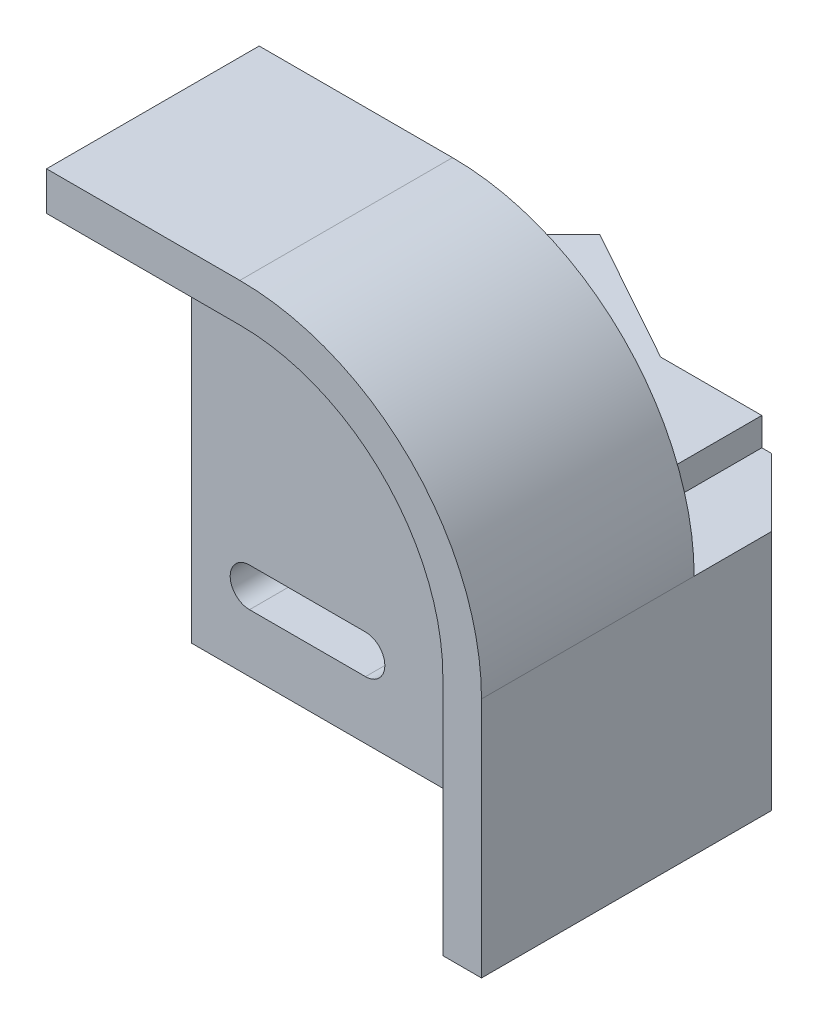
SolidWorks part; units mm, degrees
ref_plane "Front Plane" through (0, 0, 0) normal (0, 0, 1) x (1, 0, 0)
ref_plane "Top Plane" through (0, 0, 0) normal (0, 1, 0) x (1, 0, 0)
ref_plane "Right Plane" through (0, 0, 0) normal (1, 0, 0) x (0, 0, -1)
sketch "Sketch1" plane through (0, 0, 0) normal (0, 0, 1) x (1, 0, 0)
  line L0 (0, 25) -> (-20, 25)
  line L1 (-20, 25) -> (-20, -25)
  line L6 (-20, -25) -> (25, -25)
  line L7 (25, -25) -> (25, 0)
  arc A1 (25, 0) -> (0, 25) centre (0, 0) ccw
  dimension "D1" = 25
  dimension "D2" = 45
  dimension "D3" = 50
extrude "Boss-Extrude1" add sketch "Sketch1" along normal blind 7
sketch "Sketch3" plane through (0, 0, 7) normal (0, 0, 1) x (1, 0, 0)
  line L0 (25, -25) -> (25, 0) construction
  line L1 (0, 25) -> (-20, 25) construction
  line L2 (25, -25) -> (25, 0)
  line L3 (0, 25) -> (-20, 25)
  arc A0 (25, 0) -> (0, 25) centre (0, 0) ccw construction
  arc A1 (25, 0) -> (0, 25) centre (0, 0) ccw
extrude "Extrude-Thin2" add sketch "Sketch3" along normal blind 15 thin thin type one direction reverse wall 4
fillet "Fillet1" radius 7 3 edges at (-10, 21, 7) (14.8492, 14.8492, 7) (21, -12.5, 7)
sketch "Sketch5" plane through (25, 0, 0) normal (1, 0, 0) x (0, 0, -1)
  line L1 (0, -25) -> (15, -25)
  line L2 (0, -25) -> (0, 0)
  line L3 (0, 0) -> (15, 0)
  line L4 (15, -25) -> (15, 0)
  dimension "D1" = 15
extrude "Boss-Extrude2" add sketch "Sketch5" against normal blind 8
sketch "Sketch8" plane through (0, 0, 7) normal (0, 0, 1) x (1, 0, 0)
  line L0 (-20, -17) -> (-2, -17) construction
  line L1 (-20, 14) -> (-20, -25) construction
  line L2 (-20, -25) -> (14, -25) construction
  line L3 (-14, -15) -> (-2, -15)
  line L5 (-14, -19) -> (-2, -19)
  arc A0 (-2, -19) -> (-2, -15) centre (-2, -17) ccw
  arc A1 (-14, -15) -> (-14, -19) centre (-14, -17) ccw
  arc A2 (-2, -15) -> (-4, -17) centre (-2, -17) ccw construction
  arc A3 (-4, -17) -> (-2, -19) centre (-2, -17) ccw construction
  arc A4 (-12, -17) -> (-14, -15) centre (-14, -17) ccw construction
  arc A5 (-14, -19) -> (-12, -17) centre (-14, -17) ccw construction
  dimension "D1" = 4
  dimension "D2" = 12
  dimension "D3" = 6
  dimension "D4" = 8
extrude "Cut-Extrude2" cut sketch "Sketch8" against normal through all
pattern_linear "LPattern1" count 2 spacing 26 along (0, 1, 0) of "Cut-Extrude2"
chamfer "Chamfer3" distance 7 angle 45 1 edges at (25, -12.5, -15)
sketch "Sketch9" plane through (17, 0, 0) normal (-1, 0, 0) x (0, 0, 1)
  line L0 (0, 0) -> (0, -25) construction
  line L1 (-15, 0) -> (0, 0)
  line L2 (-15, 0) -> (-15, -7)
  line L3 (-15, -7) -> (0, -7)
  line L4 (0, 0) -> (0, -7)
  dimension "D1" = 7
extrude "Boss-Extrude3" add sketch "Sketch9" along normal blind 15
sketch "Sketch10" plane through (0, -7, 0) normal (0, -1, 0) x (1, 0, 0)
  line L0 (2, -15) -> (-6.9706, -15)
  line L1 (-6.9706, -15) -> (-12.6274, -9.3431)
  line L2 (-12.6274, -9.3431) -> (-16.8701, -13.5858)
  line L3 (-16.8701, -13.5858) -> (-20, -10.4558)
  line L4 (-6.9706, -7.9289) -> (-10.5061, -11.4645) construction
  line L5 (-20, -10.4558) -> (-20, 0)
  line L6 (-20, 0) -> (17, 0)
  line L7 (17, 0) -> (17, -15)
  line L8 (17, -15) -> (2, -15)
  line L9 (-4.8492, -10.0503) -> (-9.0919, -5.8076)
  line L10 (-9.0919, -5.8076) -> (-6.9706, -3.6863)
  line L11 (-6.9706, -3.6863) -> (-2.7279, -7.9289)
  line L12 (-2.7279, -7.9289) -> (-4.8492, -10.0503)
  line L14 (4.3431, -34.799) -> (-16.8701, -13.5858) construction
  dimension "D1" = 3
  dimension "D2" = 5
  dimension "D3" = 6
extrude "Boss-Extrude4" add sketch "Sketch10" against normal offset from surface 2 and the other way blind 2
sketch "Sketch13" plane through (-10.9853, 0, -10.9853) normal (-0.7071, 0, -0.7071) x (-0.7071, 0, 0.7071)
  line L0 (2.3223, -9) -> (2.3223, 2.9) construction
  line L1 (-5.6777, 2.9) -> (2.3223, 2.9)
  line L2 (-5.6777, 2.9) -> (-5.6777, 0.9)
  line L3 (-5.6777, 0.9) -> (2.3223, 0.9)
  line L4 (2.3223, 2.9) -> (2.3223, 0.9)
  line L5 (2.3223, 0.9) -> (-27.6777, 0.9) construction
  line L6 (2.3223, -9) -> (-5.6777, -9) construction
  line L7 (2.3223, -9) -> (-5.6777, -9)
  line L8 (2.3223, -9) -> (2.3223, -7)
  line L9 (2.3223, -7) -> (-5.6777, -7)
  line L10 (-5.6777, -9) -> (-5.6777, -7)
  line L11 (-5.6777, -9) -> (-5.6777, 2.9) construction
  line L12 (2.3223, -7) -> (-27.6777, -7) construction
extrude "Boss-Extrude6" add sketch "Sketch13" along normal up to surface (6 mm away) up to face at (-18.435, -3.05, -12.0208)
chamfer "Chamfer6" distance 13.5 angle 29 2 edges at (-6.9706, -8, -15) (-6.9706, 1.9, -15)
chamfer "Chamfer7" distance 3 angle 45 4 edges at (-1.5, 2.9, 0) (17, -9, -7.5) (17, -17, 0) (-1.5, -9, 0)
sketch "Sketch14" plane through (-10.9853, 0, -10.9853) normal (-0.7071, 0, -0.7071) x (-0.7071, 0, 0.7071)
  circle A0 centre (-0.6777, -3.05) radius 1.5
  dimension "D1" = 3
extrude "Cut-Extrude3" cut sketch "Sketch14" against normal blind 15
sketch "Sketch15" plane through (-15.2279, 0, -15.2279) normal (-0.7071, 0, -0.7071) x (-0.7071, 0, 0.7071)
  line L0 (2.3223, -7) -> (2.3223, 0.9) construction
  line L1 (2.6223, 1.2) -> (-12.3777, 1.2)
  line L2 (2.6223, 1.2) -> (2.6223, -7.3)
  line L3 (2.6223, -7.3) -> (-12.3777, -7.3)
  line L4 (-12.3777, 1.2) -> (-12.3777, -7.3)
  line L5 (-10.7659, -7) -> (2.3223, -7) construction
  line L6 (2.3223, 0.9) -> (-10.7659, 0.9) construction
  dimension "D1" = 0.3
  dimension "D2" = 15
  dimension "D3" = 0.3
  dimension "D4" = 0.3
extrude "Cut-Extrude4" cut sketch "Sketch15" against normal up to surface (6 mm away) up to face at (-11.5668, -3.05, -10.4038)
